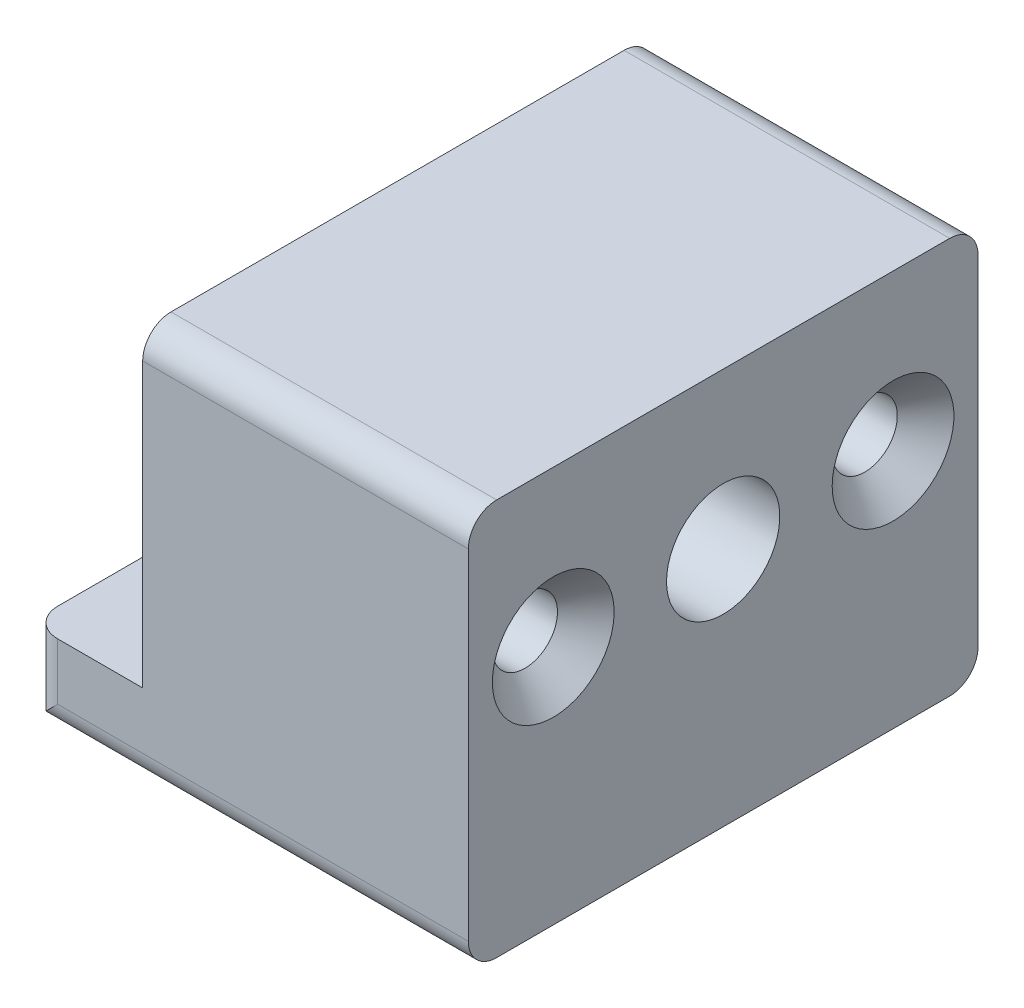
SolidWorks part; units mm, degrees
material "ABS"
ref_plane "前视基准面" through (0, 0, 0) normal (0, 0, 1) x (1, 0, 0)
ref_plane "上视基准面" through (0, 0, 0) normal (0, 1, 0) x (1, 0, 0)
ref_plane "右视基准面" through (0, 0, 0) normal (1, 0, 0) x (0, 0, -1)
sketch "草图2" plane through (0, 0, 0) normal (0, 0, 1) x (1, 0, 0)
  line L1 (-10, -7) -> (10, -7)
  line L2 (-10, -7) -> (-10, 7)
  line L3 (-10, 7) -> (10, 7)
  line L4 (10, -7) -> (10, 7)
  line L5 (-10, -7) -> (10, 7) construction
  line L6 (-10, 7) -> (10, -7) construction
  point P0 (0, 0)
  dimension "D1" = 14
  dimension "D2" = 20
extrude "凸台-拉伸1" add sketch "草图2" along normal blind 18
sketch "草图6" plane through (0, -7, 0) normal (0, -1, 0) x (1, 0, 0)
  line L0 (0, 0) -> (0, 18) construction
  line L1 (-10, 18) -> (10, 18) construction
  line L2 (10, 9) -> (-10, 9) construction
  line L3 (10, 18) -> (10, 0) construction
  line L4 (-10, 18) -> (-10, 0) construction
  circle A0 centre (0, 9) radius 4.4
  dimension "D1" = 8.8
extrude "切除-拉伸4" cut sketch "草图6" against normal blind 1.5
dome "圆顶1" faces to dome 1 distance 1 reverse direction yes elliptical dome no face at (0, -5.5, 4.6) parameters "D1"=1
sketch "草图7" plane through (0, -7, 0) normal (0, -1, 0) x (1, 0, 0)
  line L0 (-10, 0) -> (10, 0) construction
  line L1 (9.5, 0) -> (10, 0)
  line L2 (9.5, 0) -> (9.5, 18)
  line L3 (9.5, 18) -> (10, 18)
  line L4 (10, 0) -> (10, 18)
  dimension "D1" = 0.5
extrude "切除-拉伸5" cut sketch "草图7" against normal blind 20
sketch "草图8" plane through (0, -7, 0) normal (0, -1, 0) x (1, 0, 0)
  line L0 (-10, 18) -> (9.5, 18) construction
  line L1 (-10, 0) -> (-6, 0)
  line L2 (-10, 0) -> (-10, 18)
  line L3 (-10, 18) -> (-6, 18)
  line L4 (-6, 0) -> (-6, 18)
  dimension "D1" = 4
extrude "切除-拉伸6" cut sketch "草图8" against normal blind 27
sketch "草图12" plane through (-6, 0, 0) normal (-1, 0, 0) x (0, 0, 1)
  line L0 (0, 7) -> (0, -7) construction
  line L1 (18, 7) -> (0, 7)
  line L2 (18, 7) -> (18, -4)
  line L3 (18, -4) -> (0, -4)
  line L4 (0, 7) -> (0, -4)
  line L5 (0, -7) -> (18, -7) construction
  dimension "D1" = 3
extrude "切除-拉伸9" cut sketch "草图12" against normal blind 4
sketch "草图13" plane through (-2, 0, 0) normal (-1, 0, 0) x (0, 0, 1)
  line L0 (0, 7) -> (18, -4) construction
  line L1 (0, -4) -> (18, 7) construction
  line L2 (18, 7) -> (0, 7) construction
  line L3 (18, -4) -> (18, 7) construction
  line L4 (0, 7) -> (0, -4) construction
  circle A0 centre (9, 1.5) radius 2
  circle A1 centre (3, 1.5) radius 1.15
  circle A2 centre (15, 1.5) radius 1.15
  dimension "D1" = 4
  dimension "D2" = 2.3
  dimension "D3" = 2.3
  dimension "D4" = 3
  dimension "D5" = 3
extrude "切除-拉伸10" cut sketch "草图13" against normal blind 15.5
sketch "草图14" plane through (-2, 0, 0) normal (-1, 0, 0) x (0, 0, 1)
  circle A0 centre (9, 1.5) radius 4.4
  dimension "D1" = 8.8
extrude "切除-拉伸11" cut sketch "草图14" against normal blind 1
chamfer "倒角1" distance 1 angle 45 2 edges at (9.5, 1.5, 4.15) (9.5, 1.5, 16.15)
fillet "圆角1" radius 1 6 edges at (1.75, -7, 18) (1.75, -7, 0) (-6, -5.5, 18) (-6, -5.5, 0) (3.75, 7, 0) (3.75, 7, 18)
